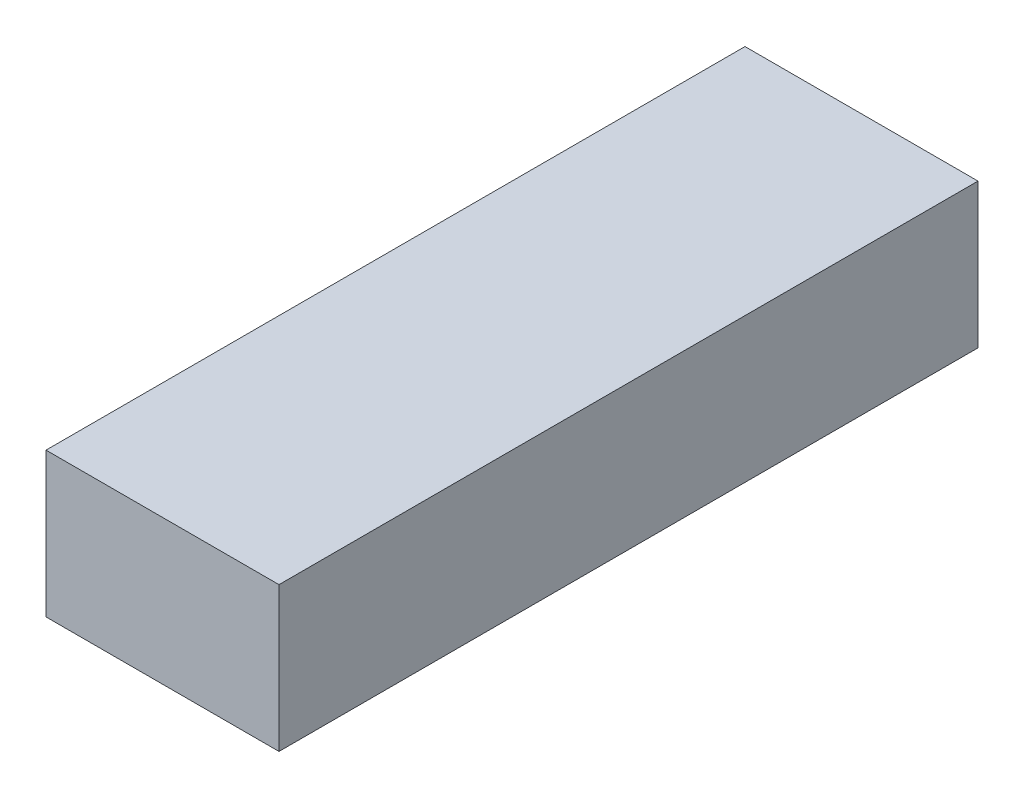
SolidWorks part; units mm, degrees
ref_plane "Front Plane" through (0, 0, 0) normal (0, 0, 1) x (1, 0, 0)
ref_plane "Top Plane" through (0, 0, 0) normal (0, 1, 0) x (1, 0, 0)
ref_plane "Right Plane" through (0, 0, 0) normal (1, 0, 0) x (0, 0, -1)
sketch "Sketch3" plane through (0, 0, 0) normal (0, 1, 0) x (1, 0, 0)
  line L1 (0, 0) -> (35, 0)
  line L2 (0, 0) -> (0, 105)
  line L3 (0, 105) -> (35, 105)
  line L4 (35, 0) -> (35, 105)
  dimension "D1" = 105
  dimension "D2" = 35
extrude "Boss-Extrude1" add sketch "Sketch3" along normal blind 21.7
